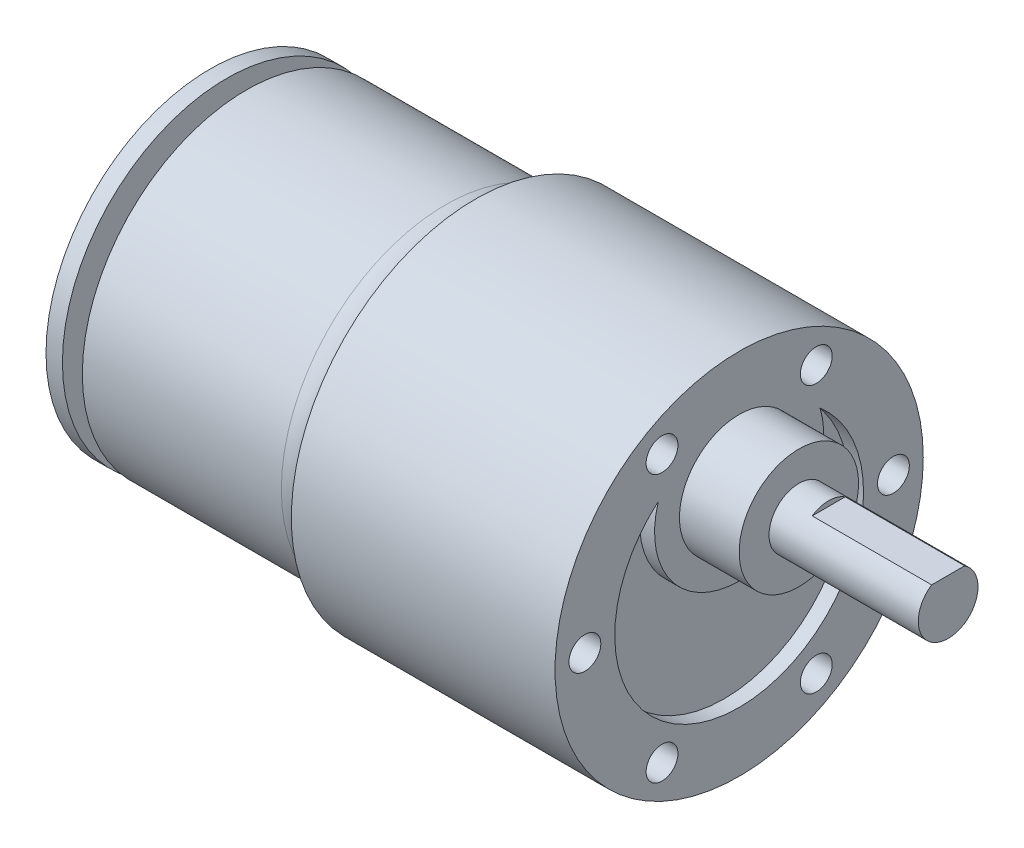
SolidWorks part; units mm, degrees
ref_plane "Alzado" through (0, 0, 0) normal (0, 0, 1) x (1, 0, 0)
ref_plane "Planta" through (0, 0, 0) normal (0, 1, 0) x (1, 0, 0)
ref_plane "Vista lateral" through (0, 0, 0) normal (1, 0, 0) x (0, 0, -1)
sketch "Croquis motor base" plane through (0, 0, 0) normal (1, 0, 0) x (0, 0, -1)
  circle A0 centre (0, 0) radius 16.5
  dimension "D2" = 33
extrude "Saliente-Extruir1" add sketch "Croquis motor base" along normal blind 23
fillet "Redondeo1" radius 3 1 edges at (23, 0, -16.5)
sketch "Croquis reductor base" plane through (23, 0, 0) normal (1, 0, 0) x (0, 0, -1)
  circle A0 centre (0, 0) radius 18.5
  dimension "D1" = 37
extrude "Saliente-Extruir2" add sketch "Croquis reductor base" along normal blind 26.5
sketch "Croquis motor shaft" plane through (49.5, 0, 0) normal (1, 0, 0) x (0, 0, -1)
  circle A1 centre (0, 7) radius 6
  circle A2 centre (0, 7) radius 8.5
  arc A3 (-8.124, 9.5) -> (8.124, 9.5) centre (0, 0) ccw
  circle A4 centre (0, 0) radius 18.5
  dimension "D1" = 12
  dimension "D3" = 17
  dimension "D4" = 25
  dimension "D2" = 7
extrude "Saliente-Extruir3" add sketch "Croquis motor shaft" along normal blind 6 contours A1
extrude "Cortar-Extruir1" cut sketch "Croquis motor shaft<3>" against normal blind 1.5 contours A2 A3 region at (49.5, -3.5996, 0)
sketch "Croquis motor shaft<3>" plane through (49.5, 0, 0) normal (1, 0, 0) x (0, 0, -1) same geometry as "Croquis motor shaft"
sketch "Croquis shaft" plane through (55.5, 0, 0) normal (1, 0, 0) x (0, 0, -1)
  circle A0 centre (0, 7) radius 3
  dimension "D1" = 6
extrude "Saliente-Extruir4" add sketch "Croquis shaft" along normal blind 15
sketch "Croquis shaft lock" plane through (70.5, 0, 0) normal (1, 0, 0) x (0, 0, -1)
  line L0 (0, 10) -> (0, 4) construction
  line L2 (-1.6583, 9.5) -> (1.6583, 9.5)
  arc A0 (1.6583, 9.5) -> (-1.6583, 9.5) centre (0, 7) ccw
  dimension "D2" = 3
  dimension "D1" = 5.5
extrude "Cortar-Extruir2" cut sketch "Croquis shaft lock" against normal blind 12
sketch "Croquis mount and close" plane through (49.5, 0, 0) normal (1, 0, 0) x (0, 0, -1)
  circle A0 centre (0, 0) radius 15.5 construction
  circle A1 centre (-15.5, 0) radius 1.6
  circle A2 centre (-7.75, 13.4234) radius 1.6
  circle A3 centre (7.75, 13.4234) radius 1.6
  circle A4 centre (15.5, 0) radius 1.6
  circle A5 centre (7.75, -13.4234) radius 1.6
  circle A6 centre (-7.75, -13.4234) radius 1.6
  dimension "D1" = 31
  dimension "D2" = 3.2
  dimension "D3" = 6
extrude "Cortar-Extruir3" cut sketch "Croquis mount and close" against normal blind 3
sketch "Croquis motor shaft out" plane through (0, 0, 0) normal (-1, 0, 0) x (0, 0, 1)
  circle A0 centre (0, 0) radius 4
  dimension "D1" = 8
extrude "Saliente-Extruir5" add sketch "Croquis motor shaft out" along normal blind 2
sketch "Croquis electronics" plane through (-2, 0, 0) normal (-1, 0, 0) x (0, 0, 1)
  circle A0 centre (0, 0) radius 16.5
  dimension "D1" = 33
extrude "Saliente-Extruir6" add sketch "Croquis electronics" along normal blind 1.65
sketch "Croquis motor axis" plane through (-3.65, 0, 0) normal (-1, 0, 0) x (0, 0, 1)
  circle A0 centre (0, 0) radius 1
  dimension "D1" = 2
extrude "Saliente-Extruir7" add sketch "Croquis motor axis" along normal blind 1.65
sketch "Croquis encoder" plane through (-5.3, 0, 0) normal (-1, 0, 0) x (0, 0, 1)
  circle A0 centre (0, 0) radius 7
  dimension "D1" = 14
extrude "Saliente-Extruir8" add sketch "Croquis encoder" along normal blind 5
